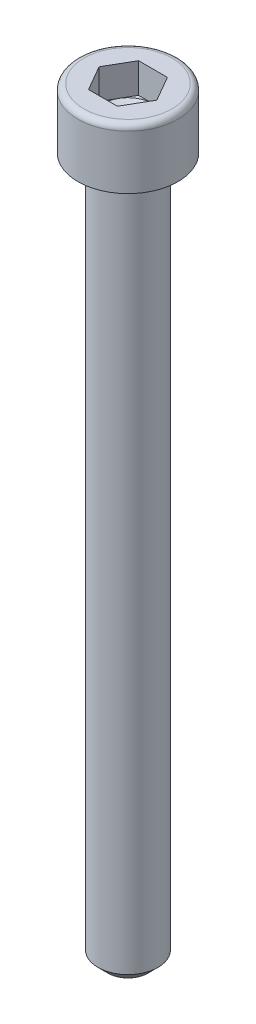
SolidWorks part; units mm, degrees
ref_plane "Face" through (0, 0, 0) normal (0, 0, 1) x (1, 0, 0)
ref_plane "Dessus" through (0, 0, 0) normal (0, 1, 0) x (1, 0, 0)
ref_plane "Droite" through (0, 0, 0) normal (1, 0, 0) x (0, 0, -1)
ref_axis "Axe" through (0, 9.8, 0) along (0, -1, 0)
sketch "Esquisse1" plane through (0, 0, 0) normal (0, 1, 0) x (1, 0, 0)
  circle A0 centre (0, 0) radius 3
  dimension "Diamètre nominal" = 6
extrude "Tige" add sketch "Esquisse1" against normal blind 70
chamfer "Chanfrein d'entrée" distance 1 angle 45 1 edges at (0, -70, 3)
sketch "Esquisse2" plane through (0, 0, 0) normal (0, 0, 1) x (1, 0, 0)
  line L0 (-5, 0) -> (5, 0) construction
  line L1 (2.5, 6) -> (2.5, 3)
  line L2 (0, 0) -> (5, 0)
  line L3 (0, 0) -> (0, 1.5566)
  line L4 (2.5, 6) -> (4.4, 6)
  line L5 (5, 0) -> (5, 5.4)
  line L6 (2.5, 3) -> (0, 1.5566)
  line L7 (0, 6) -> (0, -6.4782) construction
  line L10 (2.5, 0) -> (-2.5, 0) construction
  arc A0 (5, 5.4) -> (4.4, 6) centre (4.4, 5.4) ccw
  dimension "D2" = 0.6
  dimension "Diamètre tête" = 10
  dimension "D1" = 5
  dimension "D3" = 60
  dimension "Diamètre nominal" = 6
  dimension "Cote sur plats" = 5
  dimension "D4" = 3
  dimension "D5" = 2.5
revolve "Tête" add sketch "Esquisse2" angle 360 about L7
sketch "Esquisse3" plane through (0, 6, -3) normal (0, -1, 0) x (1, 0, 0)
  line L0 (0, 0.5) -> (0, 5.5) construction
  line L1 (0, 3) -> (-1.4434, 5.5) construction
  line L2 (0, 3) -> (-1.0825, 3.625) construction
  line L3 (0, 3) -> (-2.8868, 3) construction
  line L4 (1.4434, 5.5) -> (-1.4434, 5.5)
  line L5 (-1.4434, 5.5) -> (-2.8868, 3)
  line L6 (1.4434, 0.5) -> (-1.4434, 0.5)
  line L7 (-1.4434, 0.5) -> (-2.8868, 3)
  line L8 (1.4434, 5.5) -> (2.8868, 3)
  line L9 (1.4434, 0.5) -> (2.8868, 3)
  circle A1 centre (0, 3) radius 2.5 construction
  dimension "D1" = 30
  dimension "D2" = 30
extrude "Hexagone" cut sketch "Esquisse3" along normal blind 3
equation "\"D1@Esquisse2\" = \"Diamètre tête@Esquisse2\"/2"
equation "\"D2@Esquisse2\" = \"Diamètre nominal@Esquisse2\"*0.1"
equation "\"D4@Esquisse2\" = \"Diamètre nominal@Esquisse2\"/2"
equation "\"D5@Esquisse2\" = \"Cote sur plats@Esquisse2\"/2"
equation "\"D1@Hexagone\" = \"Diamètre nominal@Esquisse2\"/2"
